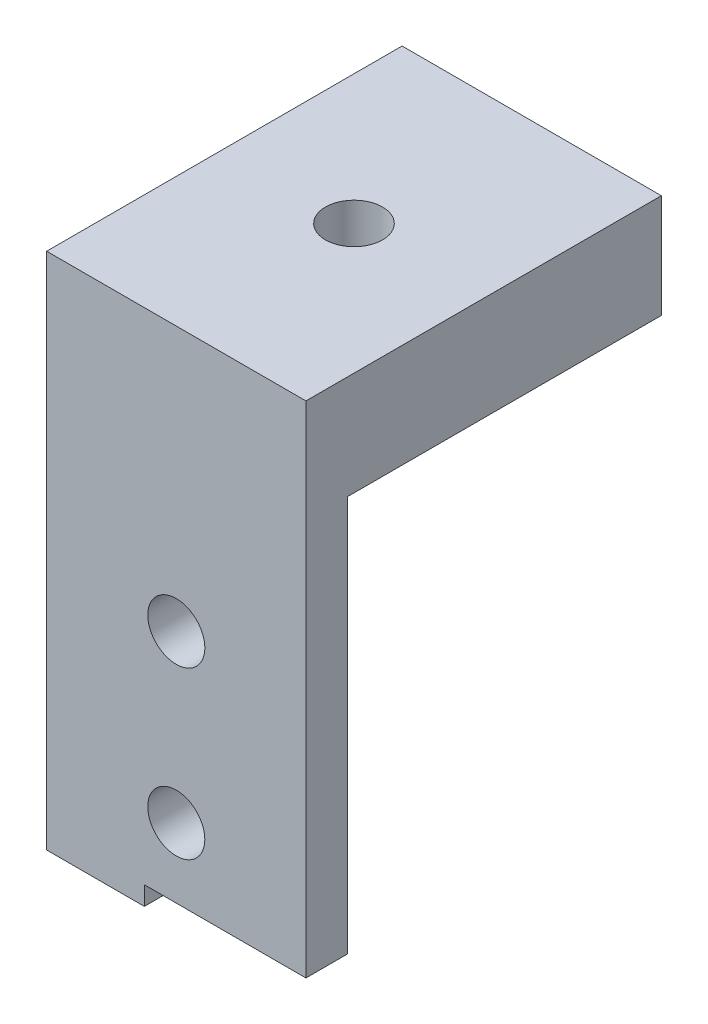
SolidWorks part; units mm, degrees
ref_plane "Front" through (0, 0, 0) normal (0, 0, 1) x (1, 0, 0)
ref_plane "Top" through (0, 0, 0) normal (0, 1, 0) x (1, 0, 0)
ref_plane "Right" through (0, 0, 0) normal (1, 0, 0) x (0, 0, -1)
sketch "Sketch1" plane through (0, 0, 0) normal (0, 1, 0) x (1, 0, 0)
  line L1 (0, 0) -> (12.5, 0)
  line L2 (0, 0) -> (0, 17.135)
  line L3 (0, 17.135) -> (12.5, 17.135)
  line L4 (12.5, 0) -> (12.5, 17.135)
  dimension "D1" = 12.5
  dimension "D2" = 17.135
extrude "tabBase" add sketch "Sketch1" along normal blind 5
sketch "Sketch2" plane through (0, 5, 0) normal (0, 1, 0) x (1, 0, 0)
  line L0 (0, 0) -> (12.5, 0) construction
  line L1 (0, 17.135) -> (0, 0) construction
  circle A0 centre (6.25, 8.5675) radius 1.375
  dimension "D1" = 2.75
  dimension "D2" = 8.5675
  dimension "D3" = 6.25
extrude "chassisMountingHole" cut sketch "Sketch2" against normal blind 5
sketch "Sketch3" plane through (0, 0, 0) normal (0, 0, 1) x (1, 0, 0)
  line L0 (12.5, 5) -> (12.5, 0) construction
  line L1 (0, 5) -> (12.5, 5)
  line L2 (0, 5) -> (0, -21)
  line L3 (0, -21) -> (12.5, -21)
  line L4 (12.5, 5) -> (12.5, -21)
  line L5 (12.5, 0) -> (0, 0) construction
  dimension "D1" = 21
extrude "frontTab" add sketch "Sketch3" against normal blind 5
sketch "frontMountingHolesSketch" plane through (0, 0, -5) normal (0, 0, -1) x (-1, 0, 0)
  line L0 (-12.5, -21) -> (-12.5, 0) construction
  line L1 (0, -21) -> (-12.5, -21) construction
  line L2 (-12.5, -10.5) -> (0, -10.5) construction
  line L3 (0, 0) -> (0, -21) construction
  circle A1 centre (-6.25, -15.75) radius 1.375
  circle A2 centre (-6.25, -7.75) radius 1.375
  point P5 (-6.25, -10.5)
  dimension "D1" = 2.75
  dimension "D2" = 5.25
  dimension "D3" = 8
extrude "frontMountingHoles" cut sketch "frontMountingHolesSketch" against normal blind 5
sketch "Sketch4" plane through (0, 0, -5) normal (0, 0, -1) x (-1, 0, 0)
  line L4 (0, 0) -> (-12.5, 0)
  line L5 (-12.5, 0) -> (-12.5, -21)
  line L6 (-12.5, -21) -> (0, -21)
  line L7 (0, -21) -> (0, 0)
  line L8 (0, 0) -> (-12.5, 0)
  line L9 (-12.5, 0) -> (-12.5, -21)
  line L10 (-12.5, -21) -> (0, -21)
  line L11 (0, -21) -> (0, 0)
  circle A0 centre (-6.25, -15.75) radius 1.375 construction
  circle A2 centre (-6.25, -15.75) radius 1.375
  circle A7 centre (-6.25, -7.75) radius 1.375
  dimension "D1" = 0
extrude "Cut-Extrude1" cut sketch "Sketch4" against normal offset from surface (3 mm away) 2 up to face at (7.625, -15.75, 0)
sketch "Sketch6" plane through (0, 0, -2) normal (0, 0, -1) x (-1, 0, 0)
  line L0 (0, 0) -> (0, -21) construction
  line L1 (-12.5, -21) -> (-4.7105, -21)
  line L2 (-12.5, -21) -> (-12.5, -19.094)
  line L3 (-12.5, -19.094) -> (-4.7105, -19.094)
  line L4 (-4.7105, -21) -> (-4.7105, -19.094)
  dimension "D1" = 4.7105
  dimension "D2" = 1.906
extrude "Cut-Extrude2" cut sketch "Sketch6" against normal blind 10
sketch "Sketch7" plane through (0, 0, -2) normal (0, 0, -1) x (-1, 0, 0)
  line L0 (-4.7105, -21) -> (-4.7105, -19.094) construction
  line L1 (0, -21) -> (-4.7105, -21)
  line L2 (0, -21) -> (0, -20)
  line L3 (0, -20) -> (-4.7105, -20)
  line L4 (-4.7105, -21) -> (-4.7105, -20)
  dimension "D1" = 1
extrude "Cut-Extrude3" cut sketch "Sketch7" against normal blind 10
